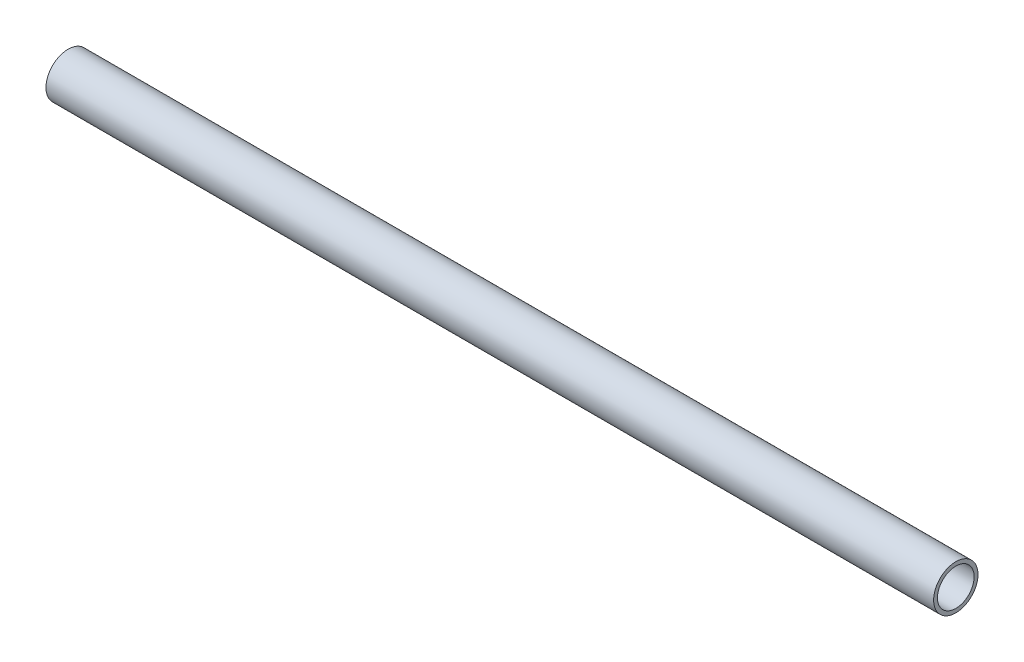
SolidWorks part; units mm, degrees
material "6061-T6 (SS)"
ref_plane "X-Y Datum" through (0, 0, 0) normal (0, 0, 1) x (1, 0, 0)
ref_plane "X-Z Datum" through (0, 0, 0) normal (0, 1, 0) x (1, 0, 0)
ref_plane "Y-Z Datum" through (0, 0, 0) normal (1, 0, 0) x (0, 0, -1)
sketch "Sketch1" plane through (0, 0, 0) normal (0, 0, 1) x (1, 0, 0)
  line L0 (0, 0) -> (381, 0)
  line L1 (55.1739, 0) -> (-55.1739, 0) construction
  dimension "D1" = 381
sweep "Sweep1" add path "Sketch1" circular profile diameter 19.05 parameters "D3"=19.05
sweep "Cut-Sweep1" cut path "Sketch1<2>" circular profile diameter 15.748 parameters "D3"=15.748
sketch "Sketch1<2>" plane through (0, 0, 0) normal (0, 0, 1) x (1, 0, 0) same geometry as "Sketch1"
